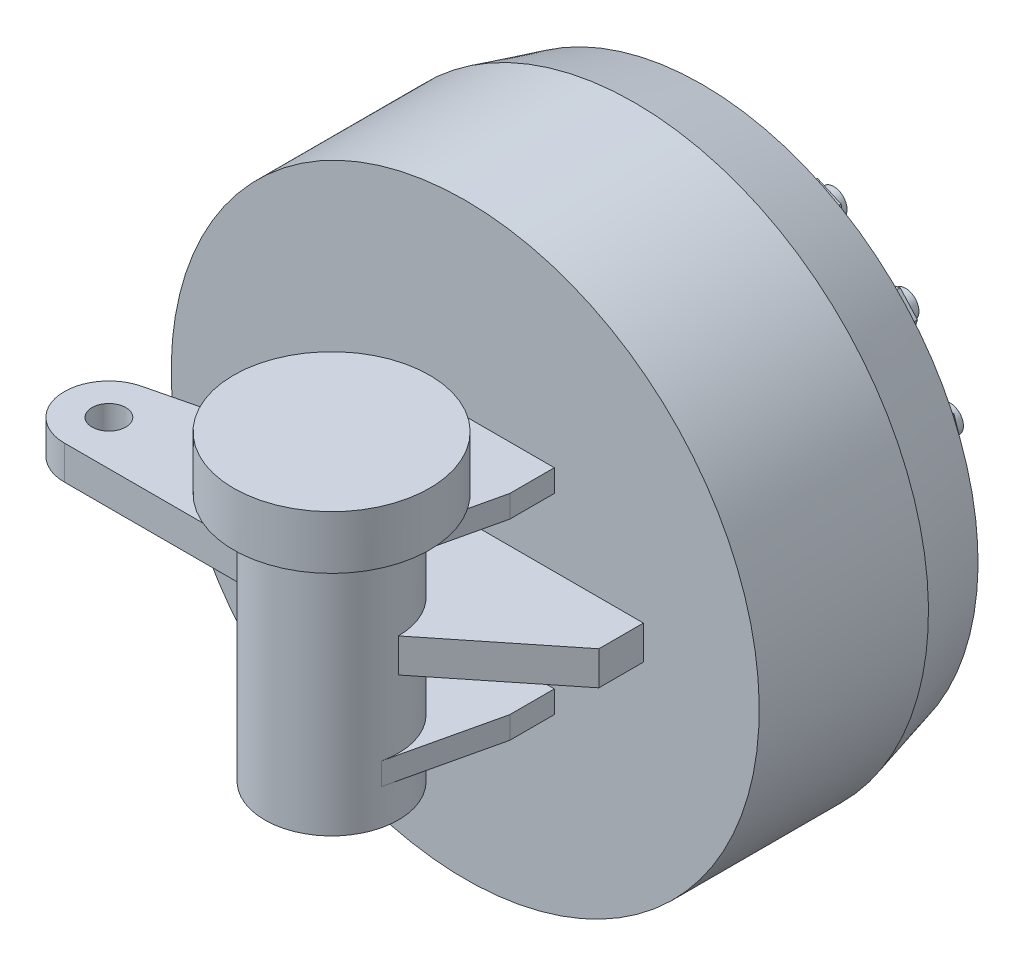
SolidWorks part; units mm, degrees
ref_plane "Front Plane" through (0, 0, 0) normal (0, 0, 1) x (1, 0, 0)
ref_plane "Top Plane" through (0, 0, 0) normal (0, 1, 0) x (1, 0, 0)
ref_plane "Right Plane" through (0, 0, 0) normal (1, 0, 0) x (0, 0, -1)
sketch "Sketch1" plane through (0, 0, 0) normal (1, 0, 0) x (0, 0, -1)
  line L0 (0, 0) -> (0, 165)
  line L1 (0, 165) -> (95, 165)
  line L2 (95, 165) -> (133, 154.8179)
  line L3 (133, 154.8179) -> (133, 75)
  line L4 (133, 75) -> (158, 75)
  line L5 (158, 75) -> (158, 50)
  line L6 (158, 50) -> (183, 50)
  line L7 (183, 50) -> (183, 0)
  line L8 (183, 0) -> (0, 0)
  dimension "D1" = 165
  dimension "D2" = 95
  dimension "D3" = 15
  dimension "D4" = 38
  dimension "D5" = 25
  dimension "D6" = 25
  dimension "D7" = 25
  dimension "D8" = 50
revolve "Revolve1" add sketch "Sketch1" angle 360 about L8
chamfer "Chamfer1" distance 4 angle 45 1 edges at (0, 50, -183)
fillet "Fillet1" radius 3.5 2 edges at (0, 75, -158) (0, 50, -158)
sketch "Sketch2" plane through (0, 0, 0) normal (0, 1, 0) x (1, 0, 0)
  circle A0 centre (0, -75) radius 37.5
  dimension "D2" = 75
  dimension "D1" = 75
extrude "Boss-Extrude1" add sketch "Sketch2" along normal blind 90 and the other way blind 80 separate body
sketch "Sketch3" plane through (0, 0, 0) normal (0, 1, 0) x (1, 0, 0)
  line L0 (-50, 0) -> (50, 0)
  line L1 (-165, 0) -> (165, 0) construction
  line L2 (50, 0) -> (50, -25)
  line L3 (50, -25) -> (36.543, -83.418)
  line L4 (0, 0) -> (0, -124.2711) construction
  line L5 (-50, -25) -> (-36.543, -83.418)
  line L6 (-50, 0) -> (-50, -25)
  line L7 (-36.543, -83.418) -> (36.543, -83.418)
  circle A1 centre (0, -75) radius 37.5 construction
  dimension "D1" = 50
  dimension "D2" = 25
extrude "Boss-Extrude2" add sketch "Sketch3" against normal blind 12.5 from offset 60
mirror "Mirror1" about plane through (0, 0, 0) normal (0, 1, 0) of "Boss-Extrude2"
sketch "Sketch4" plane through (0, 0, 0) normal (0, 1, 0) x (1, 0, 0)
  line L0 (-50, 0) -> (100, 0)
  line L1 (-165, 0) -> (165, 0) construction
  line L2 (100, 0) -> (100, -25)
  line L3 (0, -75) -> (127.4458, -75) construction
  line L4 (100, -25) -> (37.5, -75)
  line L5 (-37.5, -75) -> (-150, -75)
  line L6 (-155.8972, -25.7055) -> (-50, 0)
  circle A0 centre (0, -75) radius 37.5 construction
  arc A1 (36.543, -83.418) -> (-36.543, -83.418) centre (0, -75) ccw construction
  arc A2 (-150, -75) -> (-155.8972, -25.7055) centre (-150, -50) cw
  arc A3 (-37.5, -75) -> (37.5, -75) centre (0, -75) cw
  circle A4 centre (-150, -50) radius 9.5
  dimension "D5" = 25
  dimension "D6" = 19
  dimension "D1" = 150
  dimension "D2" = 25
  dimension "D3" = 100
  dimension "D4" = 150
extrude "Boss-Extrude3" add sketch "Sketch4" along normal mid plane 19
sketch "Sketch5" plane through (0, 60, 0) normal (0, 1, 0) x (1, 0, 0)
  circle A0 centre (0, -75) radius 55
  dimension "D1" = 110
extrude "Boss-Extrude4" add sketch "Sketch5" along normal up to surface (30 mm away) up to face at (0, 90, 112.5)
sketch "Sketch6" plane through (0, 0, -133) normal (0, 0, -1) x (-1, 0, 0)
  line L1 (14.4338, 120) -> (7.2169, 132.5)
  line L2 (7.2169, 132.5) -> (-7.2169, 132.5)
  line L3 (-7.2169, 132.5) -> (-14.4338, 120)
  line L4 (-14.4338, 120) -> (-7.2169, 107.5)
  line L5 (-7.2169, 107.5) -> (7.2169, 107.5)
  line L6 (7.2169, 107.5) -> (14.4338, 120)
  circle A0 centre (0, 120) radius 12.5 construction
  circle A1 centre (0, 120) radius 7.5
  dimension "D2" = 15
  dimension "D1" = 25
  dimension "D3" = 120
extrude "Boss-Extrude5" add sketch "Sketch6" along normal blind 25 contours A1 region at (0, 120, -133)
extrude "Boss-Extrude6" add sketch "Sketch6<3>" along normal blind 12.5 from offset 5
sketch "Sketch6<3>" plane through (0, 0, -133) normal (0, 0, -1) x (-1, 0, 0) same geometry as "Sketch6"
pattern_circular "CirPattern1" count 15 over 360 about axis through (0, 0, -133) along (0, 0, -1) of "Boss-Extrude6", "Boss-Extrude5"
